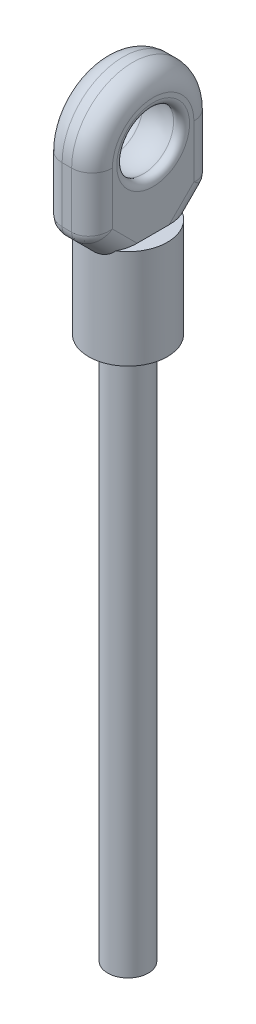
SolidWorks part; units mm, degrees
ref_plane "Front Plane" through (0, 0, 0) normal (0, 0, 1) x (1, 0, 0)
ref_plane "Top Plane" through (0, 0, 0) normal (0, 1, 0) x (1, 0, 0)
ref_plane "Right Plane" through (0, 0, 0) normal (1, 0, 0) x (0, 0, -1)
sketch "Sketch1" plane through (0, 0, 0) normal (0, 1, 0) x (1, 0, 0)
  circle A0 centre (0, 0) radius 1.5
  point P2 (0, 0)
  dimension "D1" = 3
extrude "Boss-Extrude1" add sketch "Sketch1" against normal blind 40
sketch "Sketch2" plane through (0, 0, 0) normal (0, 1, 0) x (1, 0, 0)
  circle A0 centre (0, 0) radius 2.9
extrude "Boss-Extrude2" add sketch "Sketch2" along normal blind 7.3
sketch "Sketch3" plane through (0, 0, 0) normal (1, 0, 0) x (0, 0, -1)
  line L0 (-4.5, 13) -> (-4.5, 8.5)
  line L1 (-4.5, 8.5) -> (0, 4)
  line L2 (0, 4) -> (4.5, 8.5)
  line L3 (4.5, 8.5) -> (4.5, 13)
  line L4 (-2.9, 0) -> (2.9, 0) construction
  arc A0 (4.5, 13) -> (-4.5, 13) centre (0, 13) ccw
  point P8 (0, 0)
  point P9 (0, 4.1868)
  dimension "D1" = 9
  dimension "D2" = 13
  dimension "D3" = 8.5
extrude "Boss-Extrude3" add sketch "Sketch3" along normal mid plane 3.7
fillet "Fillet1" radius 1 2 edges at (0, 8.5, -4.5) (0, 8.5, 4.5)
fillet "Fillet2" radius 1.5 14 edges at (-1.85, 7.2202, -3.2202) (-1.85, 8.5315, -4.4239) (-1.85, 7.2202, 3.2202) (-1.85, 8.5315, 4.4239) (-1.85, 10.9571, 4.5) (-1.85, 17.5, 0) (1.85, 7.2202, -3.2202) (1.85, 8.5315, -4.4239) (1.85, 7.2202, 3.2202) (1.85, 8.5315, 4.4239) (1.85, 10.9571, 4.5) (1.85, 17.5, 0) (-1.85, 10.9571, -4.5) (1.85, 10.9571, -4.5)
sketch "Sketch4" plane through (0, 0, 0) normal (1, 0, 0) x (0, 0, -1)
  line L0 (0, 15.5) -> (0, 10.5) construction
  circle A0 centre (0, 13) radius 2.5
  dimension "D1" = 5
revolve "Cut-Revolve1" cut sketch "Sketch4" angle 360 about L0 region at (0, 13, -1.061)
fillet "Fillet3" radius 0.5 2 edges at (-1.85, 13, -1.6815) (1.85, 13, -1.6815)
